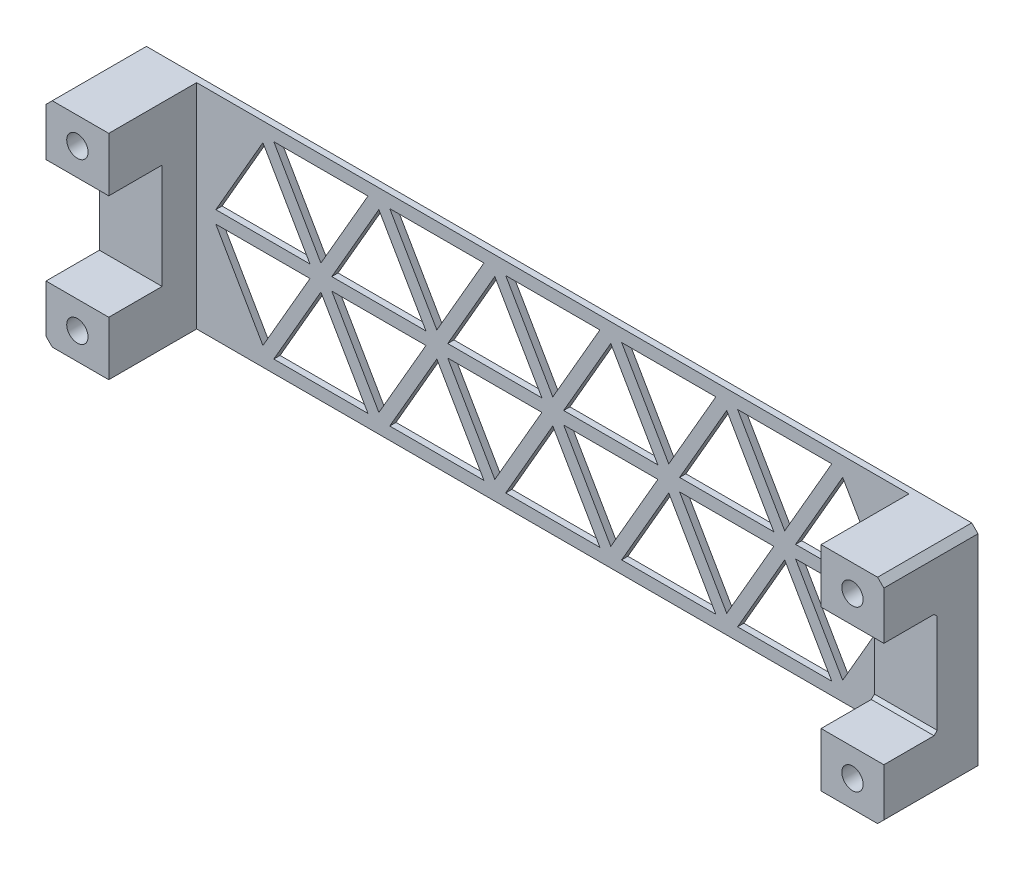
SolidWorks part; units mm, degrees
material "ABS"
ref_plane "Front Plane" through (0, 0, 0) normal (0, 0, 1) x (1, 0, 0)
ref_plane "Top Plane" through (0, 0, 0) normal (0, 1, 0) x (1, 0, 0)
ref_plane "Right Plane" through (0, 0, 0) normal (1, 0, 0) x (0, 0, -1)
ref_axis "X" through (-88.99, 0, 0) along (1, 0, 0)
ref_axis "Y" through (0, 55, 0) along (0, -1, 0)
ref_axis "Z" through (0, 0, -88.99) along (0, 0, 1)
sketch "Sketch1" plane through (0, 0, 0) normal (0, 0, 1) x (1, 0, 0)
  line L1 (-66.75, 17) -> (66.75, 17)
  line L2 (-66.75, 17) -> (-66.75, -17)
  line L3 (-66.75, -17) -> (66.75, -17)
  line L4 (66.75, 17) -> (66.75, -17)
  line L5 (-66.75, 17) -> (66.75, -17) construction
  line L6 (-66.75, -17) -> (66.75, 17) construction
  point P0 (0, 0)
  dimension "D1" = 34
  dimension "D2" = 133.5
extrude "Boss-Extrude1" add sketch "Sketch1" along normal blind 1
sketch "Sketch2" plane through (0, 0, 0) normal (0, 0, 1) x (1, 0, 0)
  line L0 (66.75, -17.125) -> (66.75, -8.375) construction
  line L1 (56.75, -8.375) -> (56.75, -17.125) construction
  line L2 (66.75, 8.375) -> (66.75, 17.125) construction
  line L3 (56.75, 17.125) -> (56.75, 8.375) construction
  line L4 (66.75, 8.375) -> (66.75, -8.375) construction
  line L5 (66.75, -8.375) -> (56.75, -8.375) construction
  line L6 (66.75, 8.375) -> (56.75, 8.375) construction
  line L7 (56.75, 8.375) -> (56.75, -8.375) construction
  line L8 (66.75, -17) -> (66.75, -8.375)
  line L9 (56.75, -8.375) -> (56.75, -17)
  line L10 (66.75, 8.375) -> (66.75, 17)
  line L11 (56.75, 17) -> (56.75, 8.375)
  line L12 (66.75, 8.375) -> (66.75, -8.375)
  line L13 (66.75, -8.375) -> (56.75, -8.375)
  line L14 (66.75, 8.375) -> (56.75, 8.375)
  line L15 (56.75, 8.375) -> (56.75, -8.375)
  line L16 (56.75, 17) -> (66.75, 17)
  line L17 (66.75, 17) -> (-66.75, 17) construction
  line L18 (56.75, -17) -> (66.75, -17)
  line L19 (-66.75, -17) -> (66.75, -17) construction
  circle A0 centre (61.75, -12.75) radius 2.25 construction
  circle A1 centre (61.75, 12.75) radius 2.25 construction
  circle A2 centre (61.75, -12.75) radius 2.25 construction
  circle A3 centre (61.75, 12.75) radius 2.25 construction
extrude "Boss-Extrude2" add sketch "Sketch2" along normal up to surface (15 mm away) contours L16 L11 L14 L10 A3 | L9 L18 L8 L13 A2 region at (61.75, -12.6875, 0) region at (61.75, 12.6875, 0)
extrude "Boss-Extrude3" add sketch "Sketch2<3>" along normal offset from surface (6.5 mm away) 8.5 contours L14 L15 L13 L12 region at (61.75, 0, 0)
sketch "Sketch2<3>" plane through (0, 0, 0) normal (0, 0, 1) x (1, 0, 0) same geometry as "Sketch2"
sketch "Sketch5" plane through (0, 0, 0) normal (0, 0, -1) x (-1, 0, 0)
  point P0 (-61.75, 12.75)
  point P3 (-61.75, -12.75)
hole_wizard "CBORE for M3 SHCS1" positions "Sketch5" profile "Sketch4" counterbore size "M3" standard "ANSI Metric" end condition through all
sketch "Sketch4" plane through (61.75, 12.75, 0) normal (1, 0, 0) x (0, 1, 0)
  line L0 (0, 0) -> (0, 15)
  line L1 (0, 15) -> (1.7, 15)
  line L3 (1.7, 15) -> (1.7, 3)
  line L4 (1.7, 3) -> (3.25, 3)
  line L5 (3.25, 3) -> (3.25, 0)
  line L7 (3.25, 0) -> (0, 0)
  line L11 (0, -6.35) -> (0, 107.95) construction
  dimension "Thru Hole Dia." = 3.4
  dimension "Thru Hole Depth" = 15
  dimension "C'Bore Dia." = 6.5
  dimension "C'Bore Depth" = 3
chamfer "Chamfer1" distance 0.5 angle 45 2 edges at (61.75, -8.375, 6.5) (61.75, 8.375, 6.5)
mirror "Mirror1" about plane through (0, 0, 0) normal (1, 0, 0) of "CBORE for M3 SHCS1", "Boss-Extrude3", "Boss-Extrude2"
chamfer "Chamfer2" distance 0.5 angle 45 4 edges at (-65, -12.75, 0) (-65, 12.75, 0) (58.5, -12.75, 0) (58.5, 12.75, 0)
sketch "Sketch6" plane through (0, 0, 0) normal (0, 0, 1) x (1, 0, 0)
  line L8 (-8.6603, 15) -> (0, 0) construction
  line L9 (8.6603, -15) -> (17.3205, 0)
  line L10 (17.3205, 0) -> (8.6603, 15)
  line L11 (8.6603, 15) -> (-8.6603, 15)
  line L12 (-8.6603, 15) -> (-17.3205, 0)
  line L13 (-17.3205, 0) -> (-8.6603, -15)
  line L14 (-8.6603, -15) -> (8.6603, -15)
  line L15 (0, 0) -> (8.6603, 15) construction
  line L16 (0, 0) -> (17.3205, 0) construction
  line L17 (0, 0) -> (8.6603, -15) construction
  line L18 (0, 0) -> (-8.6603, -15) construction
  line L19 (0, 0) -> (-17.3205, 0) construction
  line L20 (-9.2376, 14) -> (7.5056, -15)
  line L21 (9.2376, -14) -> (-7.5056, 15)
  line L22 (7.5056, 15) -> (-9.2376, -14)
  line L23 (-7.5056, -15) -> (9.2376, 14)
  line L24 (16.7432, 1) -> (-16.7432, 1)
  line L25 (-16.7432, -1) -> (16.7432, -1)
  circle A0 centre (0, 0) radius 15 construction
  dimension "D6" = 30
  dimension "D5" = 2
extrude "Cut-Extrude1" cut sketch "Sketch6" along normal through all contours L22 L11 L21 | L24 L20 L12 | L25 L13 L22 | L24 L10 L23 | L25 L21 L9 | L23 L14 L20 region at (9.2376, -5.3333, 0) region at (0, -10.6667, 0) region at (9.2376, 5.3333, 0) region at (-9.2376, -5.3333, 0) region at (0, 10.6667, 0) region at (-9.2376, 5.3333, 0)
pattern_linear "LPattern1" count 3 spacing 18.475 along (-1, 0, 0) of "Cut-Extrude1"
mirror "Mirror2" about plane through (0, 0, 0) normal (1, 0, 0) of "LPattern1"
chamfer "Chamfer3" distance 1 angle 45 4 edges at (-66.75, -17, 7.5) (-66.75, 17, 7.5) (66.75, -17, 7.5) (66.75, 17, 7.5)
